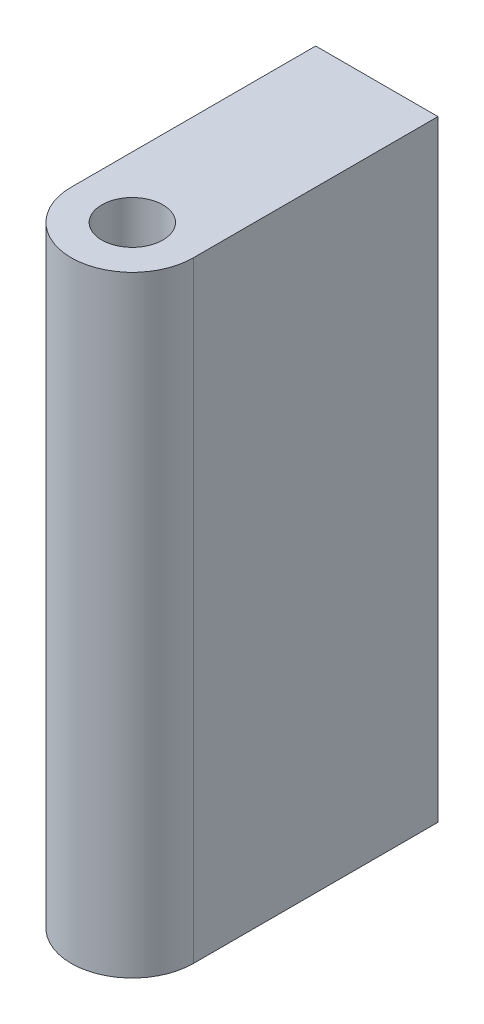
SolidWorks part; units mm, degrees
ref_plane "Front Plane" through (0, 0, 0) normal (0, 0, 1) x (1, 0, 0)
ref_plane "Top Plane" through (0, 0, 0) normal (0, 1, 0) x (1, 0, 0)
ref_plane "Right Plane" through (0, 0, 0) normal (1, 0, 0) x (0, 0, -1)
sketch "Croquis1" plane through (0, 0, 0) normal (0, 1, 0) x (1, 0, 0)
  line L0 (-0.5, 2) -> (0.5, 2)
  line L1 (0.5, 0) -> (0.5, 2)
  line L2 (-0.5, 0) -> (-0.5, 2)
  arc A0 (-0.5, 0) -> (0.5, 0) centre (0, 0) ccw
  circle A1 centre (0, 0) radius 0.25
  dimension "D1" = 0.5
  dimension "D2" = 1
  dimension "D3" = 2
extrude "Saliente-Extruir1" add sketch "Croquis1" along normal blind 2.5 and the other way blind 2.5
